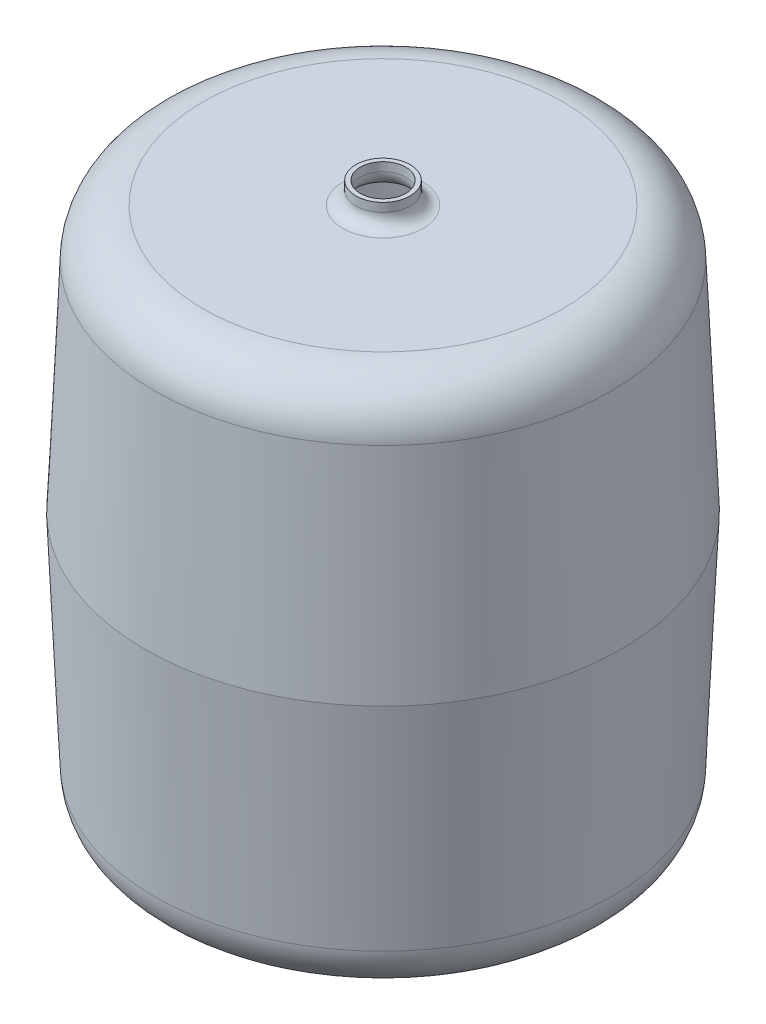
SolidWorks part; units mm, degrees
material "Alliage 1060"
ref_plane "Plan de face" through (0, 0, 0) normal (0, 0, 1) x (1, 0, 0)
ref_plane "Plan de dessus" through (0, 0, 0) normal (0, 1, 0) x (1, 0, 0)
ref_plane "Plan de droite" through (0, 0, 0) normal (1, 0, 0) x (0, 0, -1)
sketch "Esquisse1" plane through (0, 0, 0) normal (0, 0, 1) x (1, 0, 0)
  line L0 (1.1309, 254.0674) -> (1.1309, 234.0674)
  line L1 (1.1309, 234.0674) -> (-182.6191, 234.0674)
  line L2 (-182.6191, 234.0674) -> (-193.316, -10.9326)
  line L3 (-182.6191, -255.9326) -> (26.1309, -255.9326)
  line L4 (-193.316, -10.9326) -> (-182.6191, -255.9326)
  line L5 (26.1309, -255.9326) -> (26.1309, 351.9756) construction
  line L6 (1.1309, 254.0674) -> (26.1309, 254.0674)
  line L7 (26.1309, 254.0674) -> (26.1309, -255.9326)
  point P2 (1.1309, 244.0674)
  dimension "D1" = 92.5
  dimension "D2" = 92.5
  dimension "D3" = 20
  dimension "D4" = 208.75
  dimension "D5" = 490
  dimension "D6" = 245
  dimension "D7" = 25
revolve "Révolution2" add sketch "Esquisse1" angle 360 about L5
fillet "Congé1" radius 12 1 edges at (26.1309, 234.0674, -25)
fillet "Congé2" radius 45 1 edges at (26.1309, 234.0674, -208.75)
fillet "Congé3" radius 45 1 edges at (26.1309, -255.9326, -208.75)
shell "Coque12" thickness 4 removed face at (26.1309, 254.0674, -25)
equation "\"A\"= 417.5"
equation "\"B\"= 490"
equation "\"D4@Esquisse1\"=\"A\"/2"
equation "\"D5@Esquisse1\"=\"B\""
equation "\"D6@Esquisse1\"=\"B\"/2"
